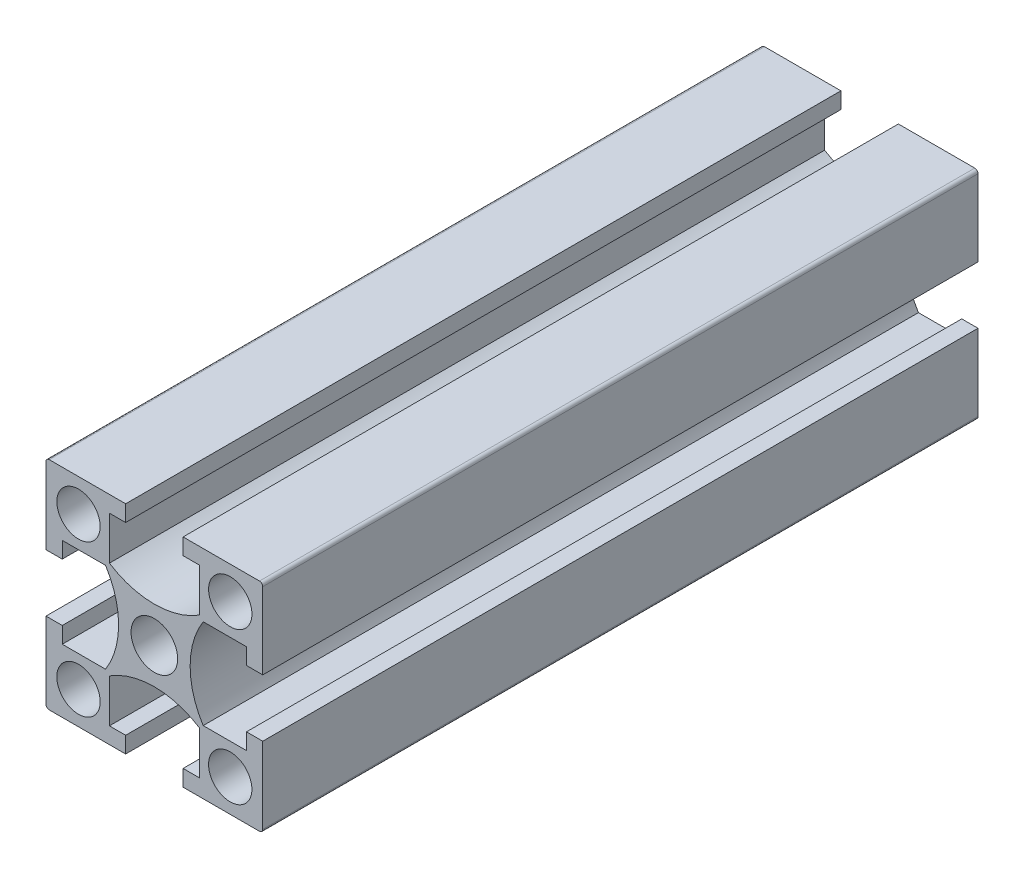
SolidWorks part; units mm, degrees
material "3.0255 (EN-AW 1350A)"
ref_plane "정면" through (0, 0, 0) normal (0, 0, 1) x (1, 0, 0)
ref_plane "윗면" through (0, 0, 0) normal (0, 1, 0) x (1, 0, 0)
ref_plane "우측면" through (0, 0, 0) normal (1, 0, 0) x (0, 0, -1)
sketch "스케치1" plane through (0, 0, 0) normal (0, 0, 1) x (1, 0, 0)
  line L0 (0, 32.0265) -> (0, -31.6588) construction
  line L1 (-10, 10) -> (-10, -10)
  line L2 (-10, 10) -> (10, 10)
  line L3 (-10, 2.65) -> (-8.5, 2.65)
  line L4 (13.6618, 0) -> (-11.6993, 0) construction
  line L5 (-8.5, 2.65) -> (-8.5, 4.15)
  line L6 (-8.5, 4.15) -> (-4.5032, 4.15)
  line L7 (-10, -2.65) -> (-8.5, -2.65)
  line L8 (-8.5, -2.65) -> (-8.5, -4.15)
  line L9 (-8.5, -4.15) -> (-4.5032, -4.15)
  line L10 (-10, -10) -> (10, -10)
  line L11 (10, 10) -> (10, -10)
  circle A0 centre (-7, 7) radius 2
  circle A1 centre (-7, -7) radius 2
  arc A2 (-4.5032, 4.15) -> (-4.5032, -4.15) centre (-11.0587, 0) cw
  circle A3 centre (0, 0) radius 2.15
  circle A4 centre (7, 7) radius 2
  circle A5 centre (7, -7) radius 2
  point P21 (-10, 0)
  point P23 (-3.3, 0)
  point P31 (0, -10)
  point P32 (0, 10)
  dimension "D3" = 4
  dimension "D9" = 6.7
  dimension "D10" = 4.3
  dimension "D11" = 7.7587
  dimension "D1" = 20
  dimension "D2" = 20
  dimension "D4" = 14
  dimension "D5" = 14
  dimension "D6" = 5.3
  dimension "D7" = 8.3
  dimension "D8" = 1.5
extrude "보스-돌출1" add sketch "스케치1" along normal blind 66 contours A0 | A4 | A3 | A5 | A1 | A2 L6 L5 L3 L1 L7 L8 L9 | L2 L11 L10 L1 region at (-6.6069, 0, 0) region at (-7, 7, 0) region at (-7, -7, 0) region at (0, 0, 0) region at (7, 7, 0) region at (7, -7, 0)
extrude "컷-돌출1" cut sketch "스케치1<3>" along normal up to next contours A2 L6 L5 L3 L1 L7 L8 L9 region at (-6.6069, 0, 0)
sketch "스케치1<3>" plane through (0, 0, 0) normal (0, 0, 1) x (1, 0, 0) same geometry as "스케치1"
pattern_circular "원형 패턴1" count 4 over 360 about axis through (0, 0, 66) along (0, 0, -1) of "컷-돌출1" reverse direction yes
fillet "필렛1" radius 0.3 4 edges at (10, -10, 33) (-10, -10, 33) (-10, 10, 33) (10, 10, 33)
sketch "스케치3" plane through (0, 10, 0) normal (0, 1, 0) x (1, 0, 0)
  line L1 (-4.15, -66) -> (4.15, -66) construction
  line L2 (4.15, 0) -> (-4.15, 0) construction
  circle A1 centre (0, -55) radius 2.5
  circle A2 centre (0, -11) radius 2.5
  dimension "D1" = 11
  dimension "D2" = 11
extrude "컷-돌출2" cut sketch "스케치3" against normal through all
